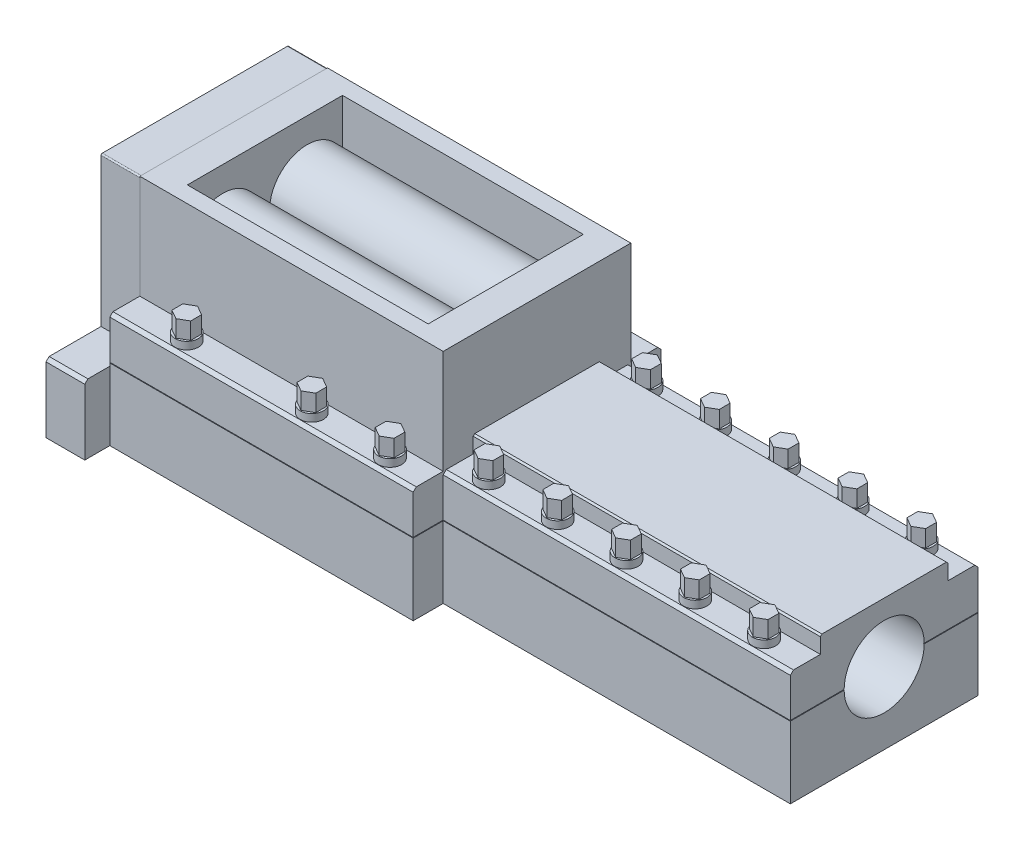
SolidWorks part; units mm, degrees
material "V2a"
ref_plane "Vorne" through (0, 0, 0) normal (0, 0, 1) x (1, 0, 0)
ref_plane "Oben" through (0, 0, 0) normal (0, 1, 0) x (1, 0, 0)
ref_plane "Rechts" through (0, 0, 0) normal (1, 0, 0) x (0, 0, -1)
sketch "Skizze1" plane through (0, 0, 0) normal (0, 0, 1) x (1, 0, 0)
  line L0 (-520, 0) -> (520, 0)
  line L1 (520, 0) -> (520, 210)
  line L2 (520, 210) -> (-35, 210)
  line L3 (-35, 210) -> (-35, 349)
  line L4 (-35, 349) -> (-520, 349)
  line L5 (-520, 349) -> (-520, 0)
  dimension "D1" = 1040
  dimension "D2" = 520
  dimension "D3" = 349
  dimension "D4" = 485
  dimension "D5" = 210
extrude "Aufsatz-Linear austragen1" add sketch "Skizze1" along normal mid plane 396
sketch "Skizze2" plane through (0, 210, 0) normal (0, 1, 0) x (1, 0, 0)
  line L0 (520, -198) -> (520, 198) construction
  line L1 (-35, 198) -> (520, 198)
  line L2 (-35, 198) -> (-35, 150)
  line L3 (-35, 150) -> (520, 150)
  line L4 (520, 198) -> (520, 150)
  line L5 (520, -198) -> (-35, -198) construction
  line L6 (520, -150) -> (-35, -150)
  line L7 (520, -150) -> (520, -198)
  line L8 (520, -198) -> (-35, -198)
  line L9 (-35, -150) -> (-35, -198)
  line L10 (-35, -198) -> (-35, 198) construction
  line L11 (0, 0) -> (520, 0) construction
  dimension "D1" = 300
extrude "Schnitt-Linear austragen1" cut sketch "Skizze2" against normal through all
sketch "Skizze3" plane through (0, 210, 0) normal (0, 1, 0) x (1, 0, 0)
  line L0 (520, -150) -> (520, 150) construction
  line L1 (-35, 150) -> (520, 150)
  line L2 (-35, 150) -> (-35, 102)
  line L3 (-35, 102) -> (520, 102)
  line L4 (520, 150) -> (520, 102)
  line L5 (-35, -198) -> (-35, 198) construction
  line L6 (520, -150) -> (-35, -150)
  line L7 (520, -150) -> (520, -102)
  line L8 (520, -102) -> (-35, -102)
  line L9 (-35, -150) -> (-35, -102)
  dimension "D1" = 48
  dimension "D2" = 48
extrude "Schnitt-Linear austragen2" cut sketch "Skizze3" against normal blind 27
sketch "Skizze4" plane through (0, 349, 0) normal (0, 1, 0) x (1, 0, 0)
  line L1 (-520, 198) -> (-35, 198)
  line L2 (-520, 198) -> (-520, 150)
  line L3 (-520, 150) -> (-35, 150)
  line L4 (-35, 198) -> (-35, 150)
  line L5 (-520, -198) -> (-520, 198) construction
  line L6 (-35, -198) -> (-520, -198)
  line L7 (-35, -198) -> (-35, -150)
  line L8 (-35, -150) -> (-520, -150)
  line L9 (-520, -198) -> (-520, -150)
  line L10 (-35, -198) -> (-35, 198) construction
  dimension "D1" = 48
  dimension "D2" = 48
extrude "Schnitt-Linear austragen3" cut sketch "Skizze4" against normal blind 166
sketch "Skizze6" plane through (520, 0, 0) normal (1, 0, 0) x (0, 0, -1)
  line L0 (0, 0) -> (0, 115) construction
  line L1 (-150, 0) -> (150, 0) construction
  circle A0 centre (0, 115) radius 64
  dimension "D2" = 128
  dimension "D1" = 115
extrude "Schnitt-Linear austragen4" cut sketch "Skizze6" against normal through all
sketch "Skizze7" plane through (0, 349, 0) normal (0, 1, 0) x (1, 0, 0)
  line L0 (-520, 0) -> (-35, 0) construction
  line L1 (-470, 124) -> (-85, 124)
  line L2 (-470, 124) -> (-470, -124)
  line L3 (-470, -124) -> (-85, -124)
  line L4 (-85, 124) -> (-85, -124)
  line L5 (-520, -150) -> (-520, 150) construction
  line L6 (-35, -150) -> (-35, 150) construction
  line L7 (-277.5, 150) -> (-277.5, -150) construction
  line L8 (-520, 150) -> (-35, 150) construction
  line L9 (-35, -150) -> (-520, -150) construction
  dimension "D1" = 385
  dimension "D2" = 248
extrude "Schnitt-Linear austragen5" cut sketch "Skizze7" against normal blind 218
sketch "Skizze8" plane through (-470, 0, 0) normal (1, 0, 0) x (0, 0, -1)
  line L0 (-150, 349) -> (150, 349) construction
  line L1 (0, 210) -> (0, 349) construction
  line L2 (-102, 210) -> (102, 210) construction
  circle A0 centre (-67.5, 249) radius 60
  circle A1 centre (67.5, 249) radius 60
  dimension "D1" = 120
  dimension "D2" = 135
  dimension "D3" = 100
extrude "Aufsatz-Linear austragen2" add sketch "Skizze8" along normal up to next
sketch "Skizze9" plane through (0, 0, -150) normal (0, 0, -1) x (-1, 0, 0)
  line L1 (265, 178) -> (375, 178)
  line L2 (265, 178) -> (265, 219)
  line L3 (265, 219) -> (375, 219)
  line L4 (375, 178) -> (375, 219)
  line L5 (35, 183) -> (35, 349) construction
  line L6 (520, 183) -> (35, 183) construction
  dimension "D1" = 230
  dimension "D2" = 110
  dimension "D3" = 41
  dimension "D4" = 5
sketch "Skizze10" plane through (520, 0, 0) normal (1, 0, 0) x (0, 0, -1)
  line L0 (-150, 0) -> (-150, 183) construction
  line L1 (-150, 115.5) -> (150, 115.5)
  line L2 (-150, 115.5) -> (-150, 114.5)
  line L3 (-150, 114.5) -> (150, 114.5)
  line L4 (150, 115.5) -> (150, 114.5)
  line L5 (150, 0) -> (150, 183) construction
  line L6 (0, 115) -> (-150, 115) construction
  dimension "D1" = 1
extrude "Schnitt-Linear austragen6" cut sketch "Skizze10" against normal blind 1
sketch "Skizze11" plane through (0, 0, -150) normal (0, 0, -1) x (-1, 0, 0)
  line L0 (35, 0) -> (35, 183) construction
  line L1 (-520, 115.5) -> (35, 115.5)
  line L2 (-520, 115.5) -> (-520, 114.5)
  line L3 (-520, 114.5) -> (35, 114.5)
  line L4 (35, 115.5) -> (35, 114.5)
  line L5 (-519, 114.5) -> (-520, 114.5) construction
extrude "Schnitt-Linear austragen7" cut sketch "Skizze11" against normal blind 1
sketch "Skizze12" plane through (0, 0, 150) normal (0, 0, 1) x (1, 0, 0)
  line L1 (520, 115.5) -> (-35, 115.5)
  line L2 (520, 115.5) -> (520, 114.5)
  line L3 (520, 114.5) -> (-35, 114.5)
  line L4 (-35, 115.5) -> (-35, 114.5)
  line L5 (519, 114.5) -> (520, 114.5) construction
extrude "Schnitt-Linear austragen8" cut sketch "Skizze12" against normal blind 1
sketch "Skizze13" plane through (-35, 0, 0) normal (1, 0, 0) x (0, 0, -1)
  line L0 (-198, 0) -> (-198, 183) construction
  line L1 (-149, 115.5) -> (-198, 115.5)
  line L2 (-149, 115.5) -> (-149, 114.5)
  line L3 (-149, 114.5) -> (-198, 114.5)
  line L4 (-198, 115.5) -> (-198, 114.5)
  line L5 (198, 0) -> (198, 183) construction
  line L6 (149, 115.5) -> (198, 115.5)
  line L7 (149, 115.5) -> (149, 114.5)
  line L8 (149, 114.5) -> (198, 114.5)
  line L9 (198, 115.5) -> (198, 114.5)
  line L10 (150, 114.5) -> (63.998, 114.5) construction
  line L11 (-150, 114.5) -> (-63.998, 114.5) construction
extrude "Schnitt-Linear austragen9" cut sketch "Skizze13" against normal blind 1
sketch "Skizze14" plane through (0, 0, 198) normal (0, 0, 1) x (1, 0, 0)
  line L0 (-520, 183) -> (-520, 0) construction
  line L1 (-35, 115.5) -> (-520, 115.5)
  line L2 (-35, 115.5) -> (-35, 114.5)
  line L3 (-35, 114.5) -> (-520, 114.5)
  line L4 (-520, 115.5) -> (-520, 114.5)
  line L5 (-36, 114.5) -> (519, 114.5) construction
extrude "Schnitt-Linear austragen10" cut sketch "Skizze14" against normal blind 1
sketch "Skizze15" plane through (0, 0, -198) normal (0, 0, -1) x (-1, 0, 0)
  line L0 (520, 183) -> (520, 0) construction
  line L1 (35, 115.5) -> (520, 115.5)
  line L2 (35, 115.5) -> (35, 114.5)
  line L3 (35, 114.5) -> (520, 114.5)
  line L4 (520, 115.5) -> (520, 114.5)
  line L5 (35, 114.5) -> (-520, 114.5) construction
extrude "Schnitt-Linear austragen11" cut sketch "Skizze15" against normal blind 1
sketch "Skizze17" plane through (-520, 0, 0) normal (-1, 0, 0) x (0, 0, 1)
  line L0 (197, 115.5) -> (197, 114.5) construction
  line L1 (-197, 115.5) -> (197, 115.5)
  line L2 (-197, 115.5) -> (-197, 114.5)
  line L3 (-197, 114.5) -> (197, 114.5)
  line L4 (197, 115.5) -> (197, 114.5)
  line L5 (197, 114.5) -> (198, 114.5) construction
extrude "Schnitt-Linear austragen12" cut sketch "Skizze17" against normal blind 1
chamfer "Fase1" distance 5 angle 45 4 edges at (-277.5, 183, 198) (-277.5, 183, -198) (242.5, 183, 150) (242.5, 183, -150)
chamfer "Fase2" distance 2.5 angle 45 2 edges at (242.5, 210, -102) (242.5, 210, 102)
sketch "Skizze18" plane through (-520, 0, 0) normal (-1, 0, 0) x (0, 0, 1)
  line L0 (198, 0) -> (-198, 0) construction
  line L1 (-128, 0) -> (-238, 0)
  line L2 (-128, 0) -> (-128, 105)
  line L3 (-133, 110) -> (-233, 110)
  line L4 (-238, 0) -> (-238, 105)
  line L5 (0, 349) -> (0, 0) construction
  line L6 (128, 0) -> (238, 0)
  line L7 (128, 0) -> (128, 105)
  line L8 (133, 110) -> (233, 110)
  line L9 (238, 0) -> (238, 105)
  line L10 (150, 349) -> (-150, 349) construction
  line L11 (-233, 110) -> (-238, 105)
  line L12 (-128, 105) -> (-133, 110)
  line L13 (128, 105) -> (133, 110)
  line L14 (233, 110) -> (238, 105)
  point P1 (-238, 110)
  point P2 (-128, 110)
  point P7 (238, 110)
  point P8 (128, 110)
  dimension "D1" = 110
  dimension "D2" = 110
  dimension "D3" = 256
extrude "Aufsatz-Linear austragen5" add sketch "Skizze18" along normal blind 62
sketch "Skizze19" plane through (0, 183, 0) normal (0, 1, 0) x (1, 0, 0)
  line L0 (-35, -198) -> (-520, -198) construction
  line L1 (520, -150) -> (-35, -150) construction
  line L2 (-35, -193) -> (-35, -150) construction
  line L3 (520, -145) -> (520, -102) construction
  line L4 (0, 0) -> (520, 0) construction
  line L5 (520, -99.5) -> (520, 99.5) construction
  circle A0 centre (454, 126) radius 18.5
  circle A1 centre (344, 126) radius 18.5
  circle A2 centre (234, 126) radius 18.5
  circle A3 centre (-421, -174) radius 18.5
  circle A4 centre (-221, -174) radius 18.5
  circle A5 centre (-96, -174) radius 18.5
  circle A6 centre (14, -126) radius 18.5
  circle A7 centre (124, -126) radius 18.5
  circle A8 centre (234, -126) radius 18.5
  circle A9 centre (344, -126) radius 18.5
  circle A10 centre (454, -126) radius 18.5
  circle A11 centre (124, 126) radius 18.5
  circle A12 centre (14, 126) radius 18.5
  circle A13 centre (-96, 174) radius 18.5
  circle A14 centre (-221, 174) radius 18.5
  circle A15 centre (-421, 174) radius 18.5
  dimension "D3" = 37
  dimension "D1" = 24
  dimension "D2" = 24
  dimension "D4" = 61
  dimension "D5" = 125
  dimension "D6" = 200
  dimension "D7" = 66
  dimension "D8" = 110
  dimension "D9" = 110
  dimension "D10" = 110
  dimension "D11" = 110
extrude "Aufsatz-Linear austragen6" add sketch "Skizze19" along normal blind 12
sketch "Skizze20" plane through (0, 195, 0) normal (0, 1, 0) x (1, 0, 0)
  line L0 (0, 0) -> (520, 0) construction
  line L1 (-406, -165.3397) -> (-421, -156.6795)
  line L2 (-421, -156.6795) -> (-436, -165.3397)
  line L3 (-436, -165.3397) -> (-436, -182.6603)
  line L4 (-436, -182.6603) -> (-421, -191.3205)
  line L5 (-421, -191.3205) -> (-406, -182.6603)
  line L6 (-406, -182.6603) -> (-406, -165.3397)
  line L7 (-206, -165.3397) -> (-221, -156.6795)
  line L8 (-221, -156.6795) -> (-236, -165.3397)
  line L9 (-236, -165.3397) -> (-236, -182.6603)
  line L10 (-236, -182.6603) -> (-221, -191.3205)
  line L11 (-221, -191.3205) -> (-206, -182.6603)
  line L12 (-206, -182.6603) -> (-206, -165.3397)
  line L13 (-81, -165.3397) -> (-96, -156.6795)
  line L14 (-96, -156.6795) -> (-111, -165.3397)
  line L15 (-111, -165.3397) -> (-111, -182.6603)
  line L16 (-111, -182.6603) -> (-96, -191.3205)
  line L17 (-96, -191.3205) -> (-81, -182.6603)
  line L18 (-81, -182.6603) -> (-81, -165.3397)
  line L19 (29, -117.3397) -> (14, -108.6795)
  line L20 (14, -108.6795) -> (-1, -117.3397)
  line L21 (-1, -117.3397) -> (-1, -134.6603)
  line L22 (-1, -134.6603) -> (14, -143.3205)
  line L23 (14, -143.3205) -> (29, -134.6603)
  line L24 (29, -134.6603) -> (29, -117.3397)
  line L25 (139, -117.3397) -> (124, -108.6795)
  line L26 (124, -108.6795) -> (109, -117.3397)
  line L27 (109, -117.3397) -> (109, -134.6603)
  line L28 (109, -134.6603) -> (124, -143.3205)
  line L29 (124, -143.3205) -> (139, -134.6603)
  line L30 (139, -134.6603) -> (139, -117.3397)
  line L31 (249, -117.3397) -> (234, -108.6795)
  line L32 (234, -108.6795) -> (219, -117.3397)
  line L33 (219, -117.3397) -> (219, -134.6603)
  line L34 (219, -134.6603) -> (234, -143.3205)
  line L35 (234, -143.3205) -> (249, -134.6603)
  line L36 (249, -134.6603) -> (249, -117.3397)
  line L37 (359, -117.3397) -> (344, -108.6795)
  line L38 (344, -108.6795) -> (329, -117.3397)
  line L39 (329, -117.3397) -> (329, -134.6603)
  line L40 (329, -134.6603) -> (344, -143.3205)
  line L41 (344, -143.3205) -> (359, -134.6603)
  line L42 (359, -134.6603) -> (359, -117.3397)
  line L43 (469, -117.3397) -> (454, -108.6795)
  line L44 (454, -108.6795) -> (439, -117.3397)
  line L45 (439, -117.3397) -> (439, -134.6603)
  line L46 (439, -134.6603) -> (454, -143.3205)
  line L47 (454, -143.3205) -> (469, -134.6603)
  line L48 (469, -134.6603) -> (469, -117.3397)
  line L49 (520, -99.5) -> (520, 99.5) construction
  line L50 (469, 134.6603) -> (469, 117.3397)
  line L51 (454, 143.3205) -> (469, 134.6603)
  line L52 (439, 134.6603) -> (454, 143.3205)
  line L53 (439, 117.3397) -> (439, 134.6603)
  line L54 (454, 108.6795) -> (439, 117.3397)
  line L55 (469, 117.3397) -> (454, 108.6795)
  line L56 (359, 134.6603) -> (359, 117.3397)
  line L57 (344, 143.3205) -> (359, 134.6603)
  line L58 (329, 134.6603) -> (344, 143.3205)
  line L59 (329, 117.3397) -> (329, 134.6603)
  line L60 (344, 108.6795) -> (329, 117.3397)
  line L61 (359, 117.3397) -> (344, 108.6795)
  line L62 (249, 134.6603) -> (249, 117.3397)
  line L63 (234, 143.3205) -> (249, 134.6603)
  line L64 (219, 134.6603) -> (234, 143.3205)
  line L65 (219, 117.3397) -> (219, 134.6603)
  line L66 (234, 108.6795) -> (219, 117.3397)
  line L67 (249, 117.3397) -> (234, 108.6795)
  line L68 (139, 134.6603) -> (139, 117.3397)
  line L69 (124, 143.3205) -> (139, 134.6603)
  line L70 (109, 134.6603) -> (124, 143.3205)
  line L71 (109, 117.3397) -> (109, 134.6603)
  line L72 (124, 108.6795) -> (109, 117.3397)
  line L73 (139, 117.3397) -> (124, 108.6795)
  line L74 (29, 134.6603) -> (29, 117.3397)
  line L75 (14, 143.3205) -> (29, 134.6603)
  line L76 (-1, 134.6603) -> (14, 143.3205)
  line L77 (-1, 117.3397) -> (-1, 134.6603)
  line L78 (14, 108.6795) -> (-1, 117.3397)
  line L79 (29, 117.3397) -> (14, 108.6795)
  line L80 (-81, 182.6603) -> (-81, 165.3397)
  line L81 (-96, 191.3205) -> (-81, 182.6603)
  line L82 (-111, 182.6603) -> (-96, 191.3205)
  line L83 (-111, 165.3397) -> (-111, 182.6603)
  line L84 (-96, 156.6795) -> (-111, 165.3397)
  line L85 (-81, 165.3397) -> (-96, 156.6795)
  line L86 (-206, 182.6603) -> (-206, 165.3397)
  line L87 (-221, 191.3205) -> (-206, 182.6603)
  line L88 (-236, 182.6603) -> (-221, 191.3205)
  line L89 (-236, 165.3397) -> (-236, 182.6603)
  line L90 (-221, 156.6795) -> (-236, 165.3397)
  line L91 (-206, 165.3397) -> (-221, 156.6795)
  line L92 (-406, 182.6603) -> (-406, 165.3397)
  line L93 (-421, 191.3205) -> (-406, 182.6603)
  line L94 (-436, 182.6603) -> (-421, 191.3205)
  line L95 (-436, 165.3397) -> (-436, 182.6603)
  line L96 (-421, 156.6795) -> (-436, 165.3397)
  line L97 (-406, 165.3397) -> (-421, 156.6795)
  circle A0 centre (-421, -174) radius 15 construction
  circle A1 centre (-221, -174) radius 15 construction
  circle A2 centre (-96, -174) radius 15 construction
  circle A3 centre (14, -126) radius 15 construction
  circle A4 centre (124, -126) radius 15 construction
  circle A5 centre (234, -126) radius 15 construction
  circle A6 centre (344, -126) radius 15 construction
  circle A7 centre (454, -126) radius 15 construction
  circle A8 centre (454, 126) radius 15 construction
  circle A9 centre (344, 126) radius 15 construction
  circle A10 centre (234, 126) radius 15 construction
  circle A11 centre (124, 126) radius 15 construction
  circle A12 centre (14, 126) radius 15 construction
  circle A13 centre (-96, 174) radius 15 construction
  circle A14 centre (-221, 174) radius 15 construction
  circle A15 centre (-421, 174) radius 15 construction
  dimension "D1" = 30
extrude "Aufsatz-Linear austragen7" add sketch "Skizze20" along normal blind 27
sketch "Skizze21" plane through (-520, 0, 0) normal (-1, 0, 0) x (0, 0, 1)
  line L0 (-150, 346.9) -> (-150, 110)
  line L1 (-133, 110) -> (-233, 110) construction
  line L2 (-150, 110) -> (-148, 110)
  line L3 (-148, 110) -> (-148, 346.9)
  line L4 (-147.9, 347) -> (147.9, 347)
  line L5 (148, 346.9) -> (148, 110)
  line L6 (233, 110) -> (133, 110) construction
  line L7 (-147.9, 349) -> (147.9, 349)
  line L8 (150, 346.9) -> (150, 110)
  line L9 (150, 110) -> (148, 110)
  arc A0 (147.9, 347) -> (148, 346.9) centre (147.9, 346.9) cw
  arc A1 (-148, 346.9) -> (-147.9, 347) centre (-147.9, 346.9) cw
  arc A2 (147.9, 349) -> (150, 346.9) centre (147.9, 346.9) cw
  arc A3 (-150, 346.9) -> (-147.9, 349) centre (-147.9, 346.9) cw
  point P20 (150, 349)
  point P23 (-150, 349)
  dimension "D4" = 0.1
  dimension "D5" = 2.1
  dimension "D1" = 2
  dimension "D2" = 2
  dimension "D3" = 2
extrude "Aufsatz-Linear austragen8" add sketch "Skizze21" along normal up to surface (62 mm away) separate body up to face at (-582, 71.6667, -183)
extrude "Aufsatz-Linear austragen10" add sketch "Skizze9" along normal blind 48
sketch "Skizze24" plane through (0, 0, 150) normal (0, 0, 1) x (1, 0, 0)
  line L0 (-35, 178) -> (-520, 178) construction
  line L1 (-375, 219) -> (-265, 219)
  line L2 (-375, 219) -> (-375, 178)
  line L3 (-375, 178) -> (-265, 178)
  line L4 (-265, 219) -> (-265, 178)
  line L5 (-35, 183) -> (-35, 349) construction
  dimension "D1" = 230
  dimension "D2" = 110
  dimension "D3" = 41
extrude "Aufsatz-Linear austragen12" [suppressed] add sketch "Skizze24" along normal blind 48
